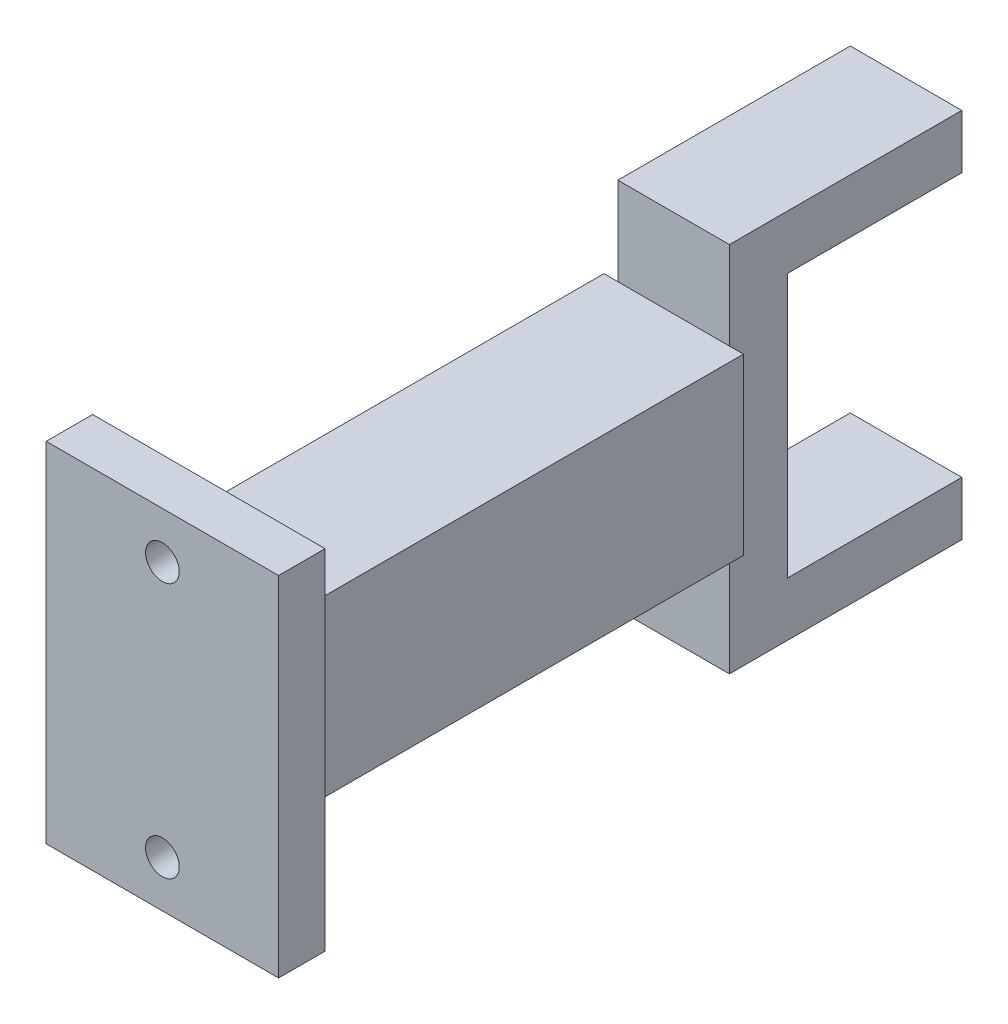
SolidWorks part; units mm, degrees
ref_plane "Спереди" through (0, 0, 0) normal (0, 0, 1) x (1, 0, 0)
ref_plane "Сверху" through (0, 0, 0) normal (0, 1, 0) x (1, 0, 0)
ref_plane "Справа" through (0, 0, 0) normal (1, 0, 0) x (0, 0, -1)
sketch "Эскиз1" plane through (0, 0, 0) normal (0, 0, 1) x (1, 0, 0)
  line L1 (-11.8051, 15.9928) -> (8.1949, 15.9928)
  line L2 (-11.8051, 15.9928) -> (-11.8051, -14.0072)
  line L3 (-11.8051, -14.0072) -> (8.1949, -14.0072)
  line L4 (8.1949, 15.9928) -> (8.1949, -14.0072)
  line L5 (-11.8051, 15.9928) -> (8.1949, -14.0072) construction
  line L6 (-11.8051, -14.0072) -> (8.1949, 15.9928) construction
  circle A0 centre (-1.8051, 11.9928) radius 1.45
  circle A3 centre (-1.8051, -10.0072) radius 1.45
  point P6 (0, 0)
  dimension "D3" = 4
  dimension "D1" = 20
  dimension "D2" = 30
  dimension "D4" = 4
  dimension "D5" = 10
  dimension "D6" = 10
extrude "Бобышка-Вытянуть1" add sketch "Эскиз1" along normal blind 4
sketch "Эскиз2" plane through (0, 0, 0) normal (0, 0, -1) x (-1, 0, 0)
  line L1 (-4.1949, 8.4928) -> (7.8051, 8.4928)
  line L2 (-4.1949, 8.4928) -> (-4.1949, -6.5072)
  line L3 (-4.1949, -6.5072) -> (7.8051, -6.5072)
  line L4 (7.8051, 8.4928) -> (7.8051, -6.5072)
  line L5 (-4.1949, 8.4928) -> (7.8051, -6.5072) construction
  line L6 (-4.1949, -6.5072) -> (7.8051, 8.4928) construction
  line L7 (-8.1949, 15.9928) -> (11.8051, 15.9928) construction
  line L8 (-8.1949, -14.0072) -> (-8.1949, 15.9928) construction
  point P0 (1.8051, 0.9928)
  point P10 (-13.3109, -5.148)
  dimension "D1" = 15
  dimension "D2" = 12
  dimension "D3" = 15
  dimension "D4" = 10
extrude "Бобышка-Вытянуть2" add sketch "Эскиз2" along normal blind 40
sketch "Эскиз3" plane through (0, 0, -40) normal (0, 0, -1) x (-1, 0, 0)
  line L0 (-4.1949, 8.4928) -> (-4.1949, -6.5072) construction
  line L1 (-2.9949, 16.0575) -> (6.6051, 16.0575)
  line L2 (-2.9949, 16.0575) -> (-2.9949, -15.9425)
  line L3 (-2.9949, -15.9425) -> (6.6051, -15.9425)
  line L4 (6.6051, 16.0575) -> (6.6051, -15.9425)
  line L5 (-2.9949, 16.0575) -> (6.6051, -15.9425) construction
  line L6 (-2.9949, -15.9425) -> (6.6051, 16.0575) construction
  point P0 (0, 0)
  point P5 (1.8051, 0.0575)
  dimension "D1" = 32
  dimension "D2" = 9.6
  dimension "D3" = 6
extrude "Бобышка-Вытянуть3" add sketch "Эскиз3" along normal blind 20
sketch "Эскиз4" plane through (0, 0, -60) normal (0, 0, -1) x (-1, 0, 0)
  line L1 (-2.9949, 11.4075) -> (6.6051, 11.4075)
  line L2 (-2.9949, 11.4075) -> (-2.9949, -11.2925)
  line L3 (-2.9949, -11.2925) -> (6.6051, -11.2925)
  line L4 (6.6051, 11.4075) -> (6.6051, -11.2925)
  line L5 (-2.9949, 11.4075) -> (6.6051, -11.2925) construction
  line L6 (-2.9949, -11.2925) -> (6.6051, 11.4075) construction
  line L8 (-2.9949, -15.9425) -> (6.6051, -15.9425) construction
  line L9 (-2.9949, 16.0575) -> (-2.9949, -15.9425) construction
  point P0 (-51.7313, 24.1124)
  point P5 (1.8051, 0.0575)
  point P8 (-2.9949, 0.0575)
  dimension "D1" = 16
  dimension "D2" = 4.8
  dimension "D3" = 9.6
  dimension "D4" = 22.7
extrude "Бобышка-Вытянуть4" add sketch "Эскиз4" against normal blind 15
extrude "Вырез-Вытянуть1" cut sketch "Эскиз4<2>" against normal blind 15
sketch "Эскиз4<2>" plane through (0, 0, -60) normal (0, 0, -1) x (-1, 0, 0) same geometry as "Эскиз4"
